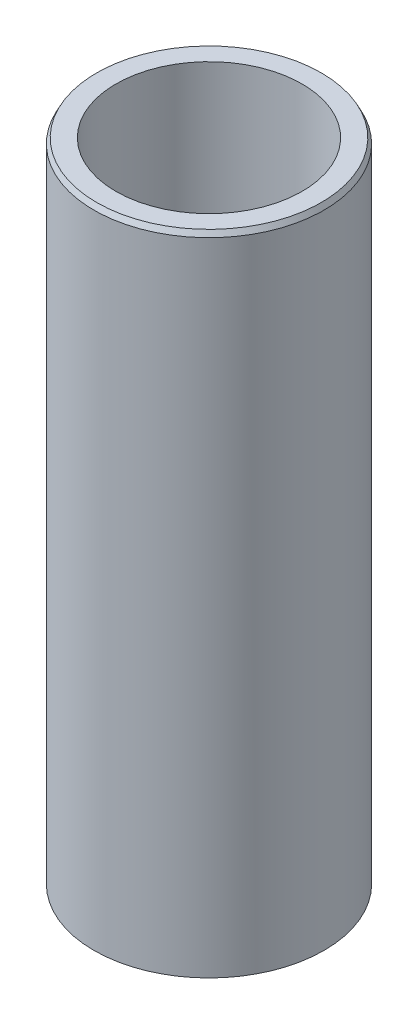
SolidWorks part; units mm, degrees
ref_plane "Front Plane" through (0, 0, 0) normal (0, 0, 1) x (1, 0, 0)
ref_plane "Top Plane" through (0, 0, 0) normal (0, 1, 0) x (1, 0, 0)
ref_plane "Right Plane" through (0, 0, 0) normal (1, 0, 0) x (0, 0, -1)
sketch "Sketch1" plane through (0, 0, 0) normal (0, 1, 0) x (1, 0, 0)
  circle A0 centre (0, 0) radius 32.5
  dimension "SHAFT_OD" = 65
extrude "Boss-Extrude1" add sketch "Sketch1" along normal blind 183.4267
sketch "Sketch2" plane through (0, 0, 0) normal (0, 1, 0) x (1, 0, 0)
  circle A0 centre (0, 0) radius 26.31
  dimension "BORE_D" = 52.62
extrude "Cut-Extrude1" cut sketch "Sketch2" along normal through all
chamfer "Chamfer1" distance 1.4993 angle 26.937 2 edges at (0, 183.4267, 32.5) (0, 0, 32.5) first distance on face at (0, 183.4267, 32.5) first distance on face at (0, 0, 26.31)
